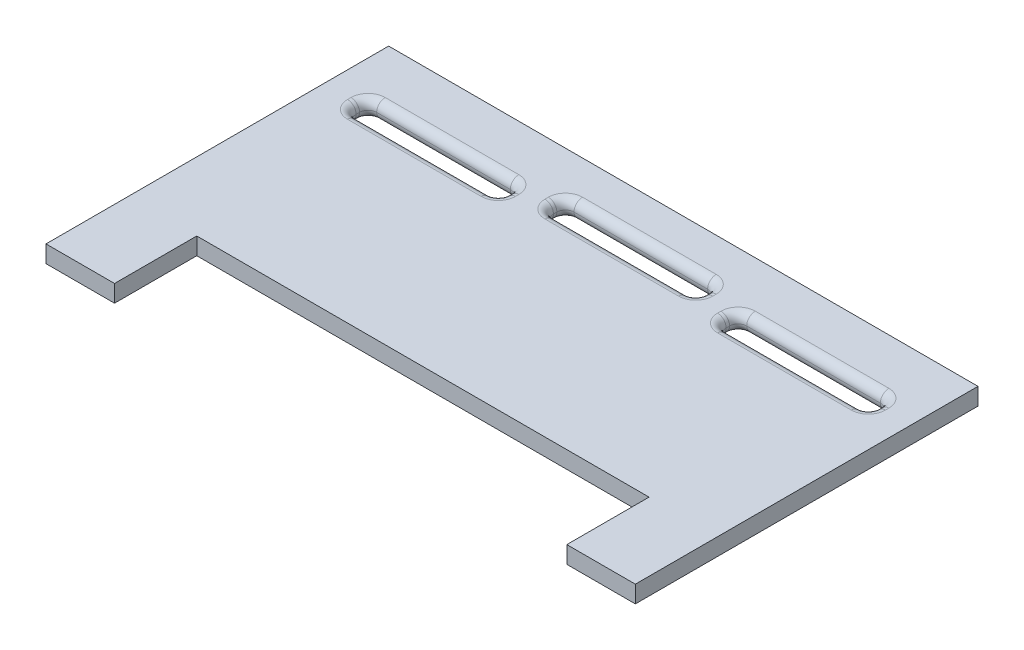
SolidWorks part; units mm, degrees
ref_plane "Front Plane" through (0, 0, 0) normal (0, 0, 1) x (1, 0, 0)
ref_plane "Top Plane" through (0, 0, 0) normal (0, 1, 0) x (1, 0, 0)
ref_plane "Right Plane" through (0, 0, 0) normal (1, 0, 0) x (0, 0, -1)
sketch "Sketch1" plane through (0, 0, 0) normal (0, 1, 0) x (1, 0, 0)
  line L0 (0, 3) -> (66, 3) construction
  line L1 (0, 0) -> (66, 0)
  line L2 (0, 0) -> (0, 38)
  line L3 (0, 38) -> (66, 38)
  line L4 (66, 0) -> (66, 38)
  line L5 (0, 22.8) -> (66, 22.8) construction
  line L6 (0, 30) -> (66, 30) construction
  line L7 (0, 31.8) -> (66, 31.8) construction
  line L8 (33, 0) -> (33, 38) construction
  dimension "D1" = 66
  dimension "D2" = 3
  dimension "D3" = 19.8
  dimension "D4" = 27
  dimension "D5" = 28.8
  dimension "D6" = 35
extrude "Boss-Extrude1" add sketch "Sketch1" along normal blind 2.5 contours L3 L4 L1 L2
sketch "Sketch2" plane through (0, 0, 0) normal (0, -1, 0) x (1, 0, 0)
  line L0 (33, 0) -> (33, -38) construction
  line L1 (0, 0) -> (66, 0) construction
  line L2 (0, -31.8) -> (66, -31.8) construction
  line L3 (22, -28.8) -> (44, -28.8)
  line L4 (22, -28.8) -> (22, -31.8)
  line L5 (22, -31.8) -> (44, -31.8)
  line L6 (44, -28.8) -> (44, -31.8)
  line L7 (0, -38) -> (66, -38) construction
  line L10 (0, -30) -> (66, -30) construction
  line L11 (-5, -30) -> (17, -30)
  line L12 (-5, -30) -> (-5, -27)
  line L13 (-5, -27) -> (17, -27)
  line L14 (17, -30) -> (17, -27)
  line L17 (71, -27) -> (49, -27)
  line L18 (49, -30) -> (49, -27)
  line L19 (71, -30) -> (49, -30)
  line L20 (71, -30) -> (71, -27)
  line L21 (33, -28.8) -> (33, -31.8) construction
  dimension "D1" = 3
  dimension "D4" = 22
  dimension "D6" = 5
  dimension "D2" = 3
  dimension "D3" = 22
sketch "Sketch3" plane through (0, 0, 0) normal (-1, 0, 0) x (0, 0, 1)
  line L0 (0, 2.5) -> (-38, 2.5) construction
  line L1 (-38, 0) -> (12, 0)
  line L2 (-38, 0) -> (-38, 2.5)
  line L3 (-38, 2.5) -> (12, 2.5)
  line L4 (12, 0) -> (12, 2.5)
  dimension "D1" = 50
ref_plane "Plane1" through (33, 0, 0) normal (1, 0, 0) x (0, 0, -1)
extrude "Boss-Extrude2" add sketch "Sketch3" along normal blind 10
mirror "Mirror1" about plane through (33, 0, 0) normal (1, 0, 0) of "Boss-Extrude2"
extrude "Cut-Extrude2" cut sketch "Sketch2" against normal through all
fillet "Fillet1" radius 1.25 24 edges at (71, 2.5, -28.5) (71, 0, -28.5) (49, 2.5, -28.5) (49, 0, -28.5) (44, 2.5, -30.3) (44, 0, -30.3) (22, 2.5, -30.3) (22, 0, -30.3) (17, 2.5, -28.5) (17, 0, -28.5) (-5, 2.5, -28.5) (-5, 0, -28.5) (60, 2.5, -30) (60, 0, -30) (60, 2.5, -27) (60, 0, -27) (33, 2.5, -31.8) (33, 0, -31.8) (33, 2.5, -28.8) (33, 0, -28.8) (6, 2.5, -30) (6, 0, -30) (6, 2.5, -27) (6, 0, -27)
